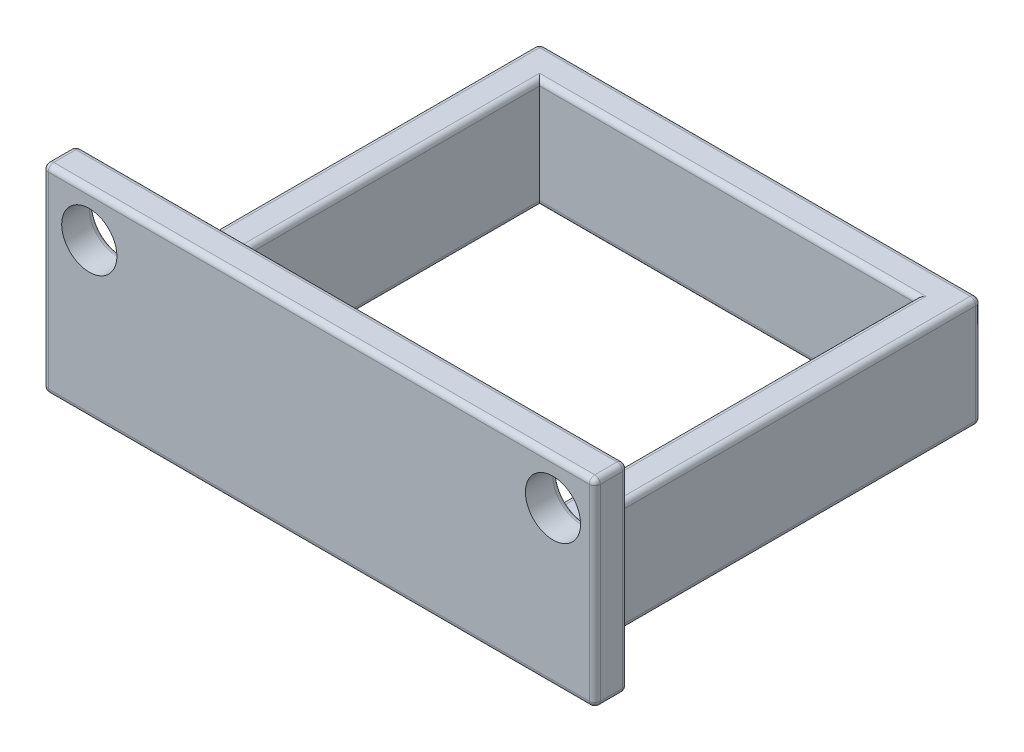
SolidWorks part; units mm, degrees
ref_plane "前视基准面" through (0, 0, 0) normal (0, 0, 1) x (1, 0, 0)
ref_plane "上视基准面" through (0, 0, 0) normal (0, 1, 0) x (1, 0, 0)
ref_plane "右视基准面" through (0, 0, 0) normal (1, 0, 0) x (0, 0, -1)
sketch "草图2" plane through (0, 0, 0) normal (0, 1, 0) x (1, 0, 0)
  line L0 (0, 0) -> (0, -17)
  line L5 (0, -17) -> (0, -20)
  line L6 (0, -17) -> (17, -17)
  line L7 (17, -17) -> (17, 17)
  line L8 (17, 17) -> (-17, 17)
  line L9 (-17, 17) -> (-17, -17)
  line L10 (-17, -17) -> (0, -17)
  line L11 (0, 17) -> (0, 20)
  line L12 (0, 20) -> (-20, 20)
  line L13 (-20, 20) -> (-20, -20)
  line L14 (-20, -20) -> (20, -20)
  line L15 (20, -20) -> (20, 20)
  line L16 (20, 20) -> (0, 20)
  line L17 (0, -20) -> (-25, -20)
  line L18 (-25, -20) -> (-25, -17)
  line L19 (-25, -17) -> (-20, -17)
  line L20 (0, -20) -> (25, -20)
  line L21 (25, -20) -> (25, -17)
  line L22 (25, -17) -> (20, -17)
  line L23 (-20, -17) -> (-17, -17)
  line L24 (17, -17) -> (20, -17)
extrude "凸台-拉伸1" add sketch "草图2" along normal blind 10 contours L13 L14 L5 L10 L9 L8 L11 L12 | L19 L18 L17 L13 | L15 L16 L11 L8 L7 L6 L5 L14 | L21 L22 L15 L20 | L23 L13 L14 L5 L10 | L24 L6 L5 L14 L15 region at (10, 0, 18.5) region at (-10, 0, 18.5) region at (17.4206, 0, 0) region at (-18.5, 0, 16.5794) region at (-22.5, 0, 18.5) region at (22.5, 0, 18.5)
extrude "凸台-拉伸2" add sketch "草图2<3>" along normal blind 18 contours L21 | L19 L18 L17 L13 | L23 L13 L14 L5 L10 | L24 L6 L5 L14 L15 region at (10, 0, 18.5) region at (-10, 0, 18.5) region at (-22.5, 0, 18.5) region at (22.5, 0, 18.5)
sketch "草图2<3>" plane through (0, 0, 0) normal (0, 1, 0) x (1, 0, 0) same geometry as "草图2"
sketch "草图4" plane through (0, 0, 17) normal (0, 0, -1) x (-1, 0, 0)
  circle A0 centre (-21.2141, 14) radius 2.5
  circle A1 centre (20.7859, 14) radius 2.5
  dimension "D1" = 5
  dimension "D4" = 5
extrude "切除-拉伸1" cut sketch "草图4" against normal blind 20
fillet "圆角1" radius 0.5 36 edges at (-25, 9, 20) (25, 9, 20) (0, 18, 20) (-25, 18, 18.5) (25, 18, 18.5) (-25, 0, 18.5) (0, 0, 20) (25, 0, 18.5) (20, 0, -1.5) (-20, 0, -1.5) (0, 0, -17) (17, 0, 0) (-17, 0, 0) (20, 10, -1.5) (17, 10, 0) (0, 10, -17) (-17, 10, 0) (-20, 10, -1.5) (20, 5, -20) (0, 10, -20) (-20, 5, -20) (0, 0, -20) (17, 5, 17) (18.5, 10, 17) (20, 5, 17) (22.5, 0, 17) (25, 9, 17) (0, 18, 17) (-25, 9, 17) (-22.5, 0, 17) (-20, 5, 17) (-18.5, 10, 17) (-17, 5, 17) (0, 0, 17) (-23.2859, 14, 17) (18.7141, 14, 17)
